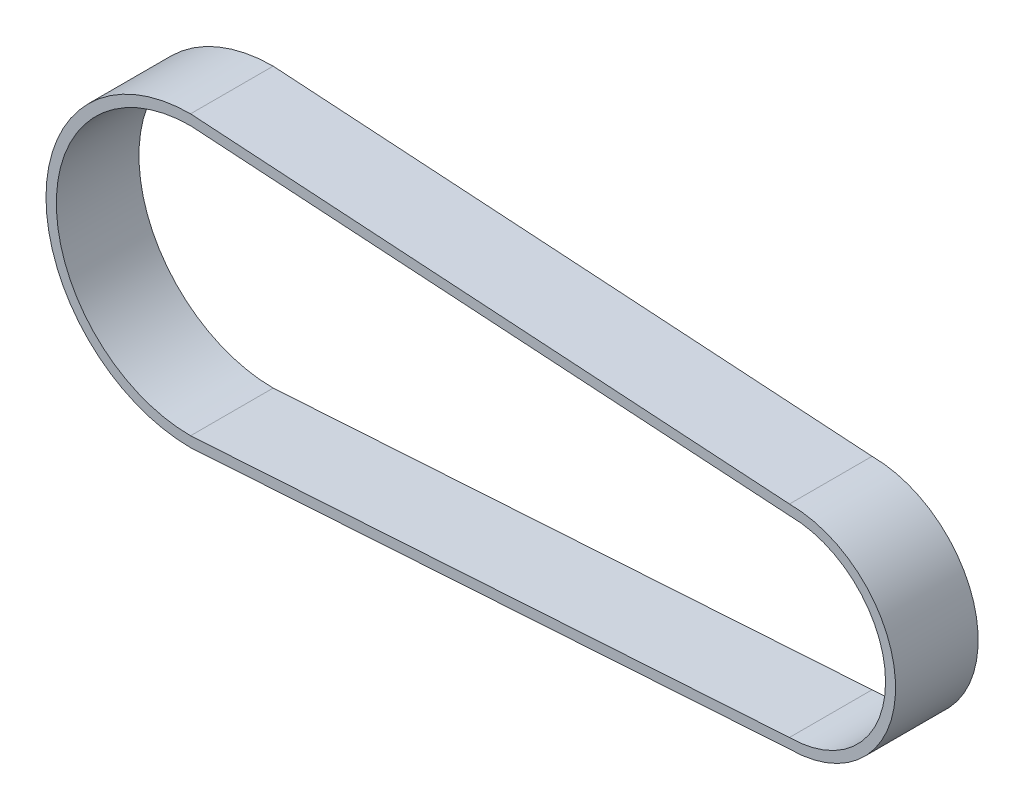
SolidWorks part; units mm, degrees
ref_plane "Plan de face" through (0, 0, 0) normal (0, 0, 1) x (1, 0, 0)
ref_plane "Plan de dessus" through (0, 0, 0) normal (0, 1, 0) x (1, 0, 0)
ref_plane "Plan de droite" through (0, 0, 0) normal (1, 0, 0) x (0, 0, -1)
sketch "Esquisse1" plane through (0, 0, 0) normal (0, 0, 1) x (1, 0, 0)
  line L0 (0, 0) -> (25, 0) construction
  line L1 (0, 0) -> (-33, 0) construction
  line L2 (-33, 13) -> (25, 9.3058)
  line L3 (-33, -14) -> (25, -10.2761)
  line L4 (-33, -13) -> (25, -9.3058)
  line L6 (-33, 14) -> (25, 10.2761)
  circle A0 centre (-33, 0) radius 13 construction
  circle A1 centre (25, 0) radius 9.3058 construction
  circle A2 centre (25, 0) radius 10.2761 construction
  circle A3 centre (-33, 0) radius 14 construction
  arc A4 (-33, 14) -> (-33, -14) centre (-33, 0) ccw
  arc A5 (-33, 13) -> (-33, -13) centre (-33, 0) ccw
  arc A6 (25, 10.2761) -> (25, -10.2761) centre (25, 0) cw
  arc A7 (25, -9.3058) -> (25, 9.3058) centre (25, 0) ccw
extrude "Boss.-Extru.1" add sketch "Esquisse1" along normal blind 8
